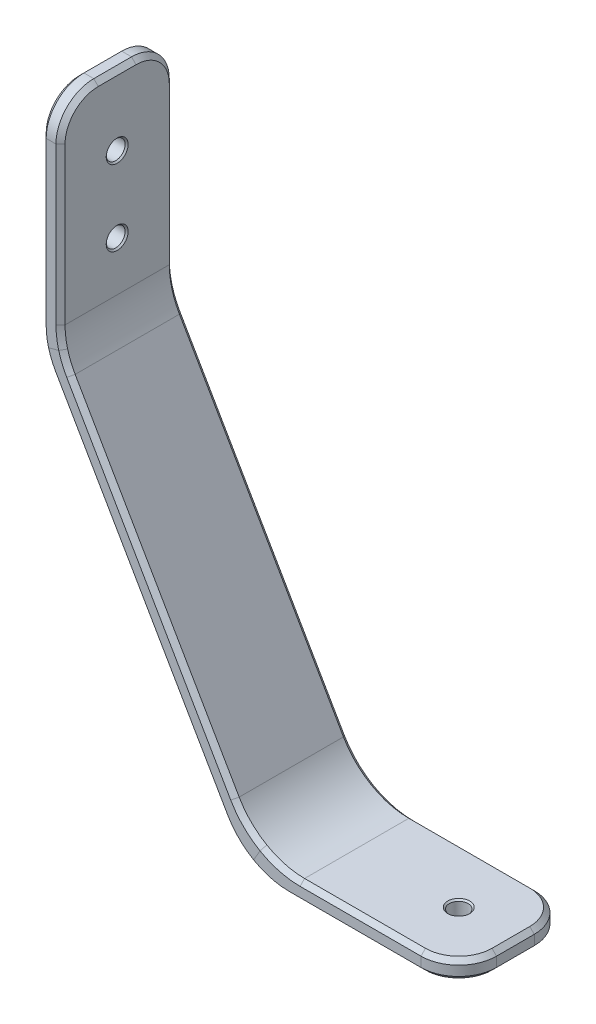
SolidWorks part; units mm, degrees
ref_plane "Front Plane" through (0, 0, 0) normal (0, 0, 1) x (1, 0, 0)
ref_plane "Top Plane" through (0, 0, 0) normal (0, 1, 0) x (1, 0, 0)
ref_plane "Right Plane" through (0, 0, 0) normal (1, 0, 0) x (0, 0, -1)
sketch "Sketch1" plane through (0, 0, 0) normal (0, 0, 1) x (1, 0, 0)
  line L0 (0, 0) -> (0, -36.5125)
  line L1 (0, -36.5125) -> (33.6108, -94.7282)
  line L2 (33.6108, -94.7282) -> (68.5358, -94.7282)
  dimension "D1" = 36.5125
  dimension "D3" = 150
  dimension "D4" = 120
  dimension "D5" = 34.925
  dimension "D2" = 58.2157
sketch "Sketch2" plane through (0, 0, 0) normal (0, 1, 0) x (1, 0, 0)
  line L1 (-1.5875, -9.525) -> (1.5875, -9.525)
  line L2 (-1.5875, -9.525) -> (-1.5875, 9.525)
  line L3 (-1.5875, 9.525) -> (1.5875, 9.525)
  line L4 (1.5875, -9.525) -> (1.5875, 9.525)
  line L5 (-1.5875, -9.525) -> (1.5875, 9.525) construction
  line L6 (-1.5875, 9.525) -> (1.5875, -9.525) construction
  point P0 (0, 0)
  dimension "D1" = 3.175
  dimension "D2" = 19.05
sweep "Sweep1" add profiles "Sketch2" path "Sketch1"
hole_wizard "1/8 (0.125) Diameter Hole1" positions "Sketch3" profile "Sketch4" hole size "1/8" standard "ANSI Inch" end condition through all
sketch "Sketch3" plane through (1.5875, 0, 0) normal (1, 0, 0) x (0, 0, -1)
  line L4 (0, 0) -> (0, -11.6936) construction
  point P0 (0, -11.6936)
  point P2 (0, -24.3936)
  dimension "D1" = 12.7
  dimension "D2" = 11.6936
sketch "Sketch4" plane through (1.5875, -11.6936, 0) normal (0, 1, 0) x (0, 0, -1)
  line L0 (0, 0) -> (0, 3.175)
  line L1 (0, 3.175) -> (1.5875, 3.175)
  line L2 (1.5875, 3.175) -> (1.5875, 0)
  line L5 (1.5875, 0) -> (0, 0)
  line L11 (0, -6.35) -> (0, 107.95) construction
  dimension "Thru Hole Dia." = 3.175
  dimension "Thru Hole Depth" = 3.175
hole_wizard "1/8 (0.125) Diameter Hole2" positions "Sketch5" profile "Sketch6" hole size "1/8" standard "ANSI Inch" end condition through all
sketch "Sketch5" plane through (0, -93.1407, 0) normal (0, 1, 0) x (1, 0, 0)
  line L0 (68.5358, -9.525) -> (68.5358, 9.525) construction
  point P0 (59.0108, 0)
  dimension "D1" = 9.525
sketch "Sketch6" plane through (59.0108, -93.1407, 0) normal (1, 0, 0) x (0, 0, 1)
  line L0 (0, 0) -> (0, 3.175)
  line L1 (0, 3.175) -> (1.5875, 3.175)
  line L2 (1.5875, 3.175) -> (1.5875, 0)
  line L5 (1.5875, 0) -> (0, 0)
  line L11 (0, -6.35) -> (0, 107.95) construction
  dimension "Thru Hole Dia." = 3.175
  dimension "Thru Hole Depth" = 3.175
fillet "Fillet1" radius 12.7 4 edges at (-1.5875, -36.9379, 0) (1.5875, -36.0871, 0) (32.6943, -96.3157, 0) (34.5274, -93.1407, 0)
fillet "Fillet2" radius 6.35 4 edges at (68.5358, -94.7282, -9.525) (68.5358, -94.7282, 9.525) (0, 0, -9.525) (0, 0, 9.525)
chamfer "Chamfer3" distance 0.762 angle 45 40 edges at (14.571, -64.9253, -9.525) (-0.6208, -38.395, -9.525) (31.0464, -92.5959, -9.525) (-1.4788, -35.1926, -9.525) (36.7396, -95.8829, -9.525) (-1.5875, -19.9425, -9.525) (51.1062, -96.3157, -9.525) (-1.5875, -1.8599, -7.6651) (66.676, -96.3157, -7.6651) (-1.5875, 0, 0) (68.5358, -96.3157, 0) (-1.5875, -1.8599, 7.6651) (66.676, -96.3157, 7.6651) (-1.5875, -19.9425, 9.525) (51.1062, -96.3157, 9.525) (-1.4788, -35.1926, 9.525) (36.7396, -95.8829, 9.525) (-0.6208, -38.395, 9.525) (31.0464, -92.5959, 9.525) (14.571, -64.9253, 9.525) (17.0751, -62.9124, -9.525) (2.5542, -37.5443, -9.525) (32.8795, -89.4209, -9.525) (1.6962, -34.3419, -9.525) (38.5727, -92.7079, -9.525) (1.5875, -19.5171, -9.525) (52.0228, -93.1407, -9.525) (1.5875, -1.8599, -7.6651) (66.676, -93.1407, -7.6651) (1.5875, 0, 0) (68.5358, -93.1407, 0) (1.5875, -1.8599, 7.6651) (66.676, -93.1407, 7.6651) (1.5875, -19.5171, 9.525) (52.0228, -93.1407, 9.525) (1.6962, -34.3419, 9.525) (38.5727, -92.7079, 9.525) (2.5542, -37.5443, 9.525) (32.8795, -89.4209, 9.525) (17.0751, -62.9124, 9.525)
chamfer "Chamfer2" distance 0.254 angle 45 6 edges at (1.5875, -24.3936, -1.5875) (-1.5875, -24.3936, -1.5875) (1.5875, -11.6936, -1.5875) (-1.5875, -11.6936, -1.5875) (59.0108, -93.1407, 1.5875) (59.0108, -96.3157, 1.5875)
equation "\"D2@Sketch1\"=2.59807621 - 0.3069935 + 0.0008725"
equation "\"D1@Sketch1\"=1.25+0.1875"
